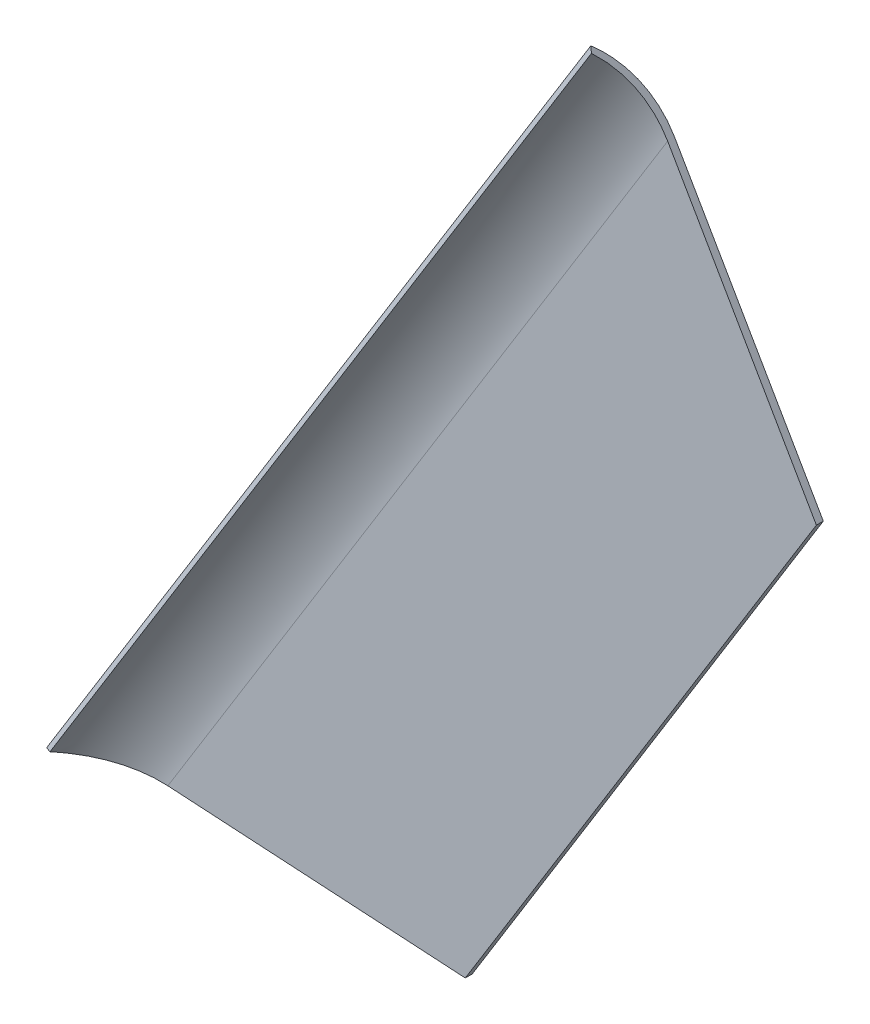
SolidWorks part; units mm, degrees
material "6061 Alloy"
ref_plane "Front Plane" through (0, 0, 0) normal (0, 0, 1) x (1, 0, 0)
ref_plane "Top Plane" through (0, 0, 0) normal (0, 1, 0) x (1, 0, 0)
ref_plane "Right Plane" through (0, 0, 0) normal (1, 0, 0) x (0, 0, -1)
sketch "Sketch1" plane through (0, 0, 0) normal (0, 0, 1) x (1, 0, 0)
  line L0 (-55.5895, -99.2786) -> (-123.6294, -95.2248)
  line L1 (24.7319, 30.5999) -> (-9.288, 89.6634)
  line L2 (-9.288, 89.6634) -> (-123.6294, -95.2248)
  line L4 (-15.4288, -34.3394) -> (-55.5895, -99.2786)
  line L5 (-15.4288, -34.3394) -> (24.7319, 30.5999)
extrude "Boss-Extrude1" add sketch "Sketch1" along normal blind 1.5875
ref_plane "Plane1" through (52.1505, 30.0381, 10.9624) normal (0.8525, 0.491, 0.1792) x (0.4974, -0.8674, 0.0105)
ref_plane "Plane2" through (-19.6299, -31.7412, 0) normal (0.526, 0.8505, 0) x (0.8505, -0.526, 0)
sketch "Sketch4" plane through (-19.6299, -31.7412, 0) normal (0.526, 0.8505, 0) x (0.8505, -0.526, 0)
  line L0 (-55.0604, -1.5875) -> (-55.0604, 0)
  line L6 (-72.746, -9.1467) -> (-72.8907, -9.0911)
  line L7 (-72.746, -9.1467) -> (-71.8916, -9.4747)
  arc A1 (-72.5485, -8.6323) -> (-72.8907, -9.0911) centre (-55.0604, -22.0307) ccw
  ellipse E3 centre (-57.186, -24.5953) end of major axis (-48.2259, -1.2562) minor radius 21.6506 (-55.0604, 0) -> (-72.5485, -8.6323) ccw
  ellipse E4 centre (-57.186, -26.1828) end of major axis (-66.1462, -49.522) minor radius 21.6506 (-55.0604, -1.5875) -> (-71.8916, -9.4747) ccw
extrude "Boss-Extrude3" add sketch "Sketch4" along normal blind 120 and the other way blind 120
ref_plane "Plane3" through (-27.3316, -15.7427, 173.1596) normal (0.1553, 0.0894, -0.9838) x (-0.9879, 0.0141, -0.1546)
ref_plane "Plane4" through (59.3222, 34.1689, 12.4699) normal (0.8525, 0.491, 0.1792) x (-0.3048, 0.1885, 0.9336)
sketch "Sketch5" plane through (0, 0, 0) normal (0, 0, -1) x (-1, 0, 0)
  line L0 (9.288, 89.6634) -> (21.8605, 111.4912)
  line L1 (21.8605, 111.4912) -> (10.3878, 118.0993)
  line L2 (10.3878, 118.0993) -> (-2.4247, 95.8548)
  line L3 (9.288, 89.6634) -> (-2.4247, 95.8548)
  line L6 (123.6294, -95.2248) -> (148.7745, -93.7266)
  line L7 (123.6294, -95.2248) -> (123.9368, -108.4696)
  line L8 (149.5619, -106.9429) -> (123.9368, -108.4696)
  line L9 (148.7745, -93.7266) -> (149.5619, -106.9429)
extrude "Cut-Extrude1" cut sketch "Sketch5" against normal through all
sketch "Sketch6" plane through (0, 0, 0) normal (0, 0, -1) x (-1, 0, 0)
  line L0 (20.3683, 108.9005) -> (145.7901, -93.9044)
  line L3 (55.5895, -99.2786) -> (145.7901, -93.9044)
  line L4 (-24.7319, 30.5999) -> (20.3683, 108.9005)
  line L10 (-24.7319, 30.5999) -> (55.5895, -99.2786)
